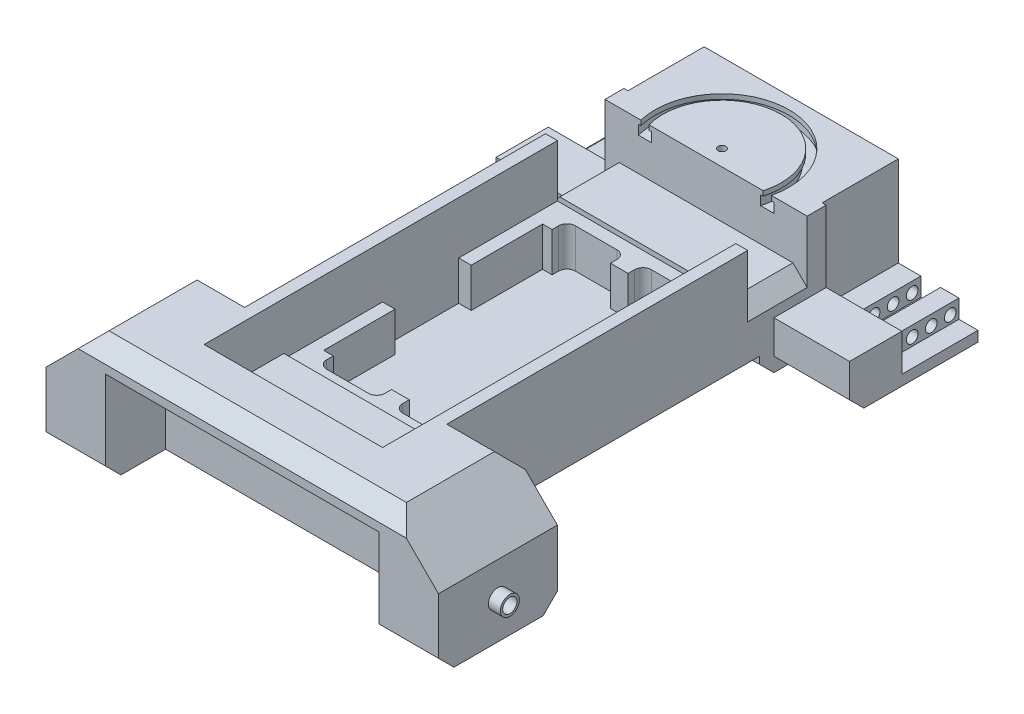
SolidWorks part; units mm, degrees
ref_plane "Front Plane" through (0, 0, 0) normal (0, 0, 1) x (1, 0, 0)
ref_plane "Top Plane" through (0, 0, 0) normal (0, 1, 0) x (1, 0, 0)
ref_plane "Right Plane" through (0, 0, 0) normal (1, 0, 0) x (0, 0, -1)
sketch "Sketch1" plane through (0, 0, 0) normal (0, 1, 0) x (1, 0, 0)
  line L1 (0, 0) -> (75, 0)
  line L2 (0, 0) -> (0, 115)
  line L3 (0, 115) -> (75, 115)
  line L4 (75, 0) -> (75, 115)
  line L5 (-5, -5) -> (80, -5)
  line L6 (-5, -5) -> (-5, 120)
  line L7 (-5, 120) -> (80, 120)
  line L8 (80, -5) -> (80, 120)
  line L9 (-5, 120) -> (80, 120)
  line L10 (-5, 120) -> (-5, 180)
  line L11 (-5, 180) -> (80, 180)
  line L12 (80, 120) -> (80, 180)
  line L13 (-5, -5) -> (80, -5)
  line L14 (-5, -5) -> (-5, -30)
  line L15 (-5, -30) -> (80, -30)
  line L16 (80, -5) -> (80, -30)
  line L17 (-5, 180) -> (-45, 180)
  line L18 (-5, 180) -> (-5, 120)
  line L19 (-5, 120) -> (-45, 120)
  line L20 (-45, 180) -> (-45, 120)
  line L21 (80, 180) -> (120, 180)
  line L22 (80, 180) -> (80, 120)
  line L23 (80, 120) -> (120, 120)
  line L24 (120, 180) -> (120, 120)
  line L25 (-5, -30) -> (-45, -30)
  line L26 (-5, -30) -> (-5, -5)
  line L27 (-5, -5) -> (-45, -5)
  line L28 (-45, -30) -> (-45, -5)
  line L29 (80, -30) -> (120, -30)
  line L30 (80, -30) -> (80, -5)
  line L31 (80, -5) -> (120, -5)
  line L32 (120, -30) -> (120, -5)
  dimension "D1" = 115
  dimension "D2" = 75
  dimension "D3" = 125
  dimension "D4" = 85
  dimension "D5" = 5
  dimension "D6" = 5
  dimension "D7" = 60
  dimension "D8" = 25
  dimension "D9" = 85
  dimension "D10" = 40
  dimension "D11" = 40
  dimension "D12" = 40
extrude "Boss-Extrude1" add sketch "Sketch1" against normal blind 22 contours L17 L20 L19 L10 | L7 L12 L11 L10 | L24 L21 L12 L23 | L5 L8 L7 L6 L4 L1 L2 L3 | L28 L25 L14 L27 | L16 L5 L14 L15 | L29 L32 L31 L16 region at (-3.4884, 0, -57.5) region at (37.5, 0, 17.5) region at (-25, 0, 17.5) region at (100, 0, 17.5) region at (37.5, 0, -150) region at (-25, 0, -150) region at (100, 0, -150)
sketch "Sketch2" plane through (0, -22, 0) normal (0, -1, 0) x (1, 0, 0)
  line L0 (5.25, -11.5) -> (69.75, -11.5)
  line L1 (0, -57.5) -> (75, -57.5)
  line L2 (0, -57.5) -> (0, -73.5)
  line L3 (0, -73.5) -> (75, -73.5)
  line L4 (75, -57.5) -> (75, -73.5)
  line L5 (0, -77.21) -> (5.25, -77.21)
  line L6 (0, 0) -> (0, -115) construction
  line L7 (75, 0) -> (75, -115) construction
  line L8 (0, -77.21) -> (0, -37.79)
  line L9 (0, -57.5) -> (75, -57.5)
  line L10 (0, -57.5) -> (0, -41.5)
  line L11 (0, -41.5) -> (75, -41.5)
  line L12 (75, -57.5) -> (75, -41.5)
  line L13 (37.5, -41.5) -> (5.25, -41.5)
  line L14 (37.5, -41.5) -> (37.5, -11.5)
  line L15 (37.5, -11.5) -> (5.25, -11.5)
  line L16 (5.25, -41.5) -> (5.25, -11.5)
  line L17 (37.5, -11.5) -> (69.75, -11.5)
  line L18 (37.5, -11.5) -> (37.5, -41.5)
  line L19 (37.5, -41.5) -> (69.75, -41.5)
  line L20 (69.75, -11.5) -> (69.75, -41.5)
  line L21 (5.25, -73.5) -> (69.75, -73.5)
  line L22 (5.25, -73.5) -> (5.25, -103.5)
  line L23 (5.25, -103.5) -> (69.75, -103.5)
  line L24 (69.75, -73.5) -> (69.75, -103.5)
  line L25 (9.275, -103.5) -> (33.775, -103.5)
  line L26 (9.275, -103.5) -> (9.275, -106.25)
  line L27 (12.775, -109.75) -> (30.275, -109.75)
  line L28 (33.775, -103.5) -> (33.775, -106.25)
  line L29 (41.223, -103.5) -> (65.723, -103.5)
  line L30 (41.223, -103.5) -> (41.223, -106.25)
  line L31 (44.723, -109.75) -> (62.223, -109.75)
  line L32 (65.723, -103.5) -> (65.723, -106.25)
  line L33 (0, -37.79) -> (5.25, -37.79)
  line L34 (5.25, -77.21) -> (5.25, -37.79)
  line L35 (69.75, -37.79) -> (75, -37.79)
  line L36 (69.75, -37.79) -> (69.75, -77.21)
  line L37 (69.75, -77.21) -> (75, -77.21)
  line L38 (75, -37.79) -> (75, -77.21)
  line L39 (65.723, -11.5) -> (65.723, -8.75)
  line L40 (44.723, -5.25) -> (62.223, -5.25)
  line L41 (41.223, -11.5) -> (41.223, -8.75)
  line L42 (33.775, -11.5) -> (33.775, -8.75)
  line L43 (12.775, -5.25) -> (30.275, -5.25)
  line L44 (9.275, -11.5) -> (9.275, -8.75)
  line L46 (0, 0) -> (75, 0)
  line L47 (0, 0) -> (0, -115)
  line L48 (0, -115) -> (75, -115)
  line L49 (75, 0) -> (75, -115)
  line L50 (-5, 5) -> (80, 5)
  line L51 (-5, 5) -> (-5, -120)
  line L52 (-5, -120) -> (80, -120)
  line L53 (80, 5) -> (80, -120)
  arc A0 (62.223, -109.75) -> (65.723, -106.25) centre (62.223, -106.25) ccw
  arc A1 (41.223, -106.25) -> (44.723, -109.75) centre (44.723, -106.25) ccw
  arc A2 (30.275, -109.75) -> (33.775, -106.25) centre (30.275, -106.25) ccw
  arc A3 (9.275, -106.25) -> (12.775, -109.75) centre (12.775, -106.25) ccw
  arc A4 (9.275, -8.75) -> (12.775, -5.25) centre (12.775, -8.75) cw
  arc A5 (30.275, -5.25) -> (33.775, -8.75) centre (30.275, -8.75) cw
  arc A6 (41.223, -8.75) -> (44.723, -5.25) centre (44.723, -8.75) cw
  arc A7 (62.223, -5.25) -> (65.723, -8.75) centre (62.223, -8.75) cw
  point P38 (9.275, -109.75)
  point P63 (9.275, -5.25)
  line M17 (80, -120) -> (80, 5)
  line M23 (-5, 5) -> (-5, -120)
  line M26 (75, 0) -> (75, -115)
  line M27 (75, -115) -> (0, -115)
  line M28 (0, -115) -> (0, 0)
  line M29 (0, 0) -> (75, 0)
  dimension "D14" = 3.5
  dimension "D1" = 16
  dimension "D2" = 75
  dimension "D3" = 16
  dimension "D6" = 32.25
  dimension "D7" = 30
  dimension "D8" = 6.25
  dimension "D9" = 24.5
  dimension "D10" = 4.025
  dimension "D11" = 24.5
  dimension "D12" = 64.5
  dimension "D13" = 4.027
  dimension "D15" = 39.42
  dimension "D16" = 3.71
  dimension "D17" = 3.71
extrude "Boss-Extrude2" add sketch "Sketch2" along normal blind 16.5 contours A3 L26 L23 L22 L5 L37 L24 L32 A0 L31 A1 L30 L28 A2 L27 M28 M27 M26 | L52 L50 L8 M23 M17 M29 M26 M27 M28 | L40 A7 L39 L17 L20 L35 L33 L16 L0 L44 A4 L43 A5 L42 L15 L41 A6 M26 M29 M28 | L24 L37 L3 M26 | L35 L20 L11 M26 | L33 L8 L11 L16 | L22 L3 L5 M28 region at (37.5004, -22, -10.9883) region at (2.625, -22, -39.645) region at (72.375, -22, -39.645) region at (2.625, -22, -75.355) region at (72.375, -22, -75.355) region at (37.5004, -22, -104.0117) region at (37.5, -22, 3.4884)
sketch "Sketch4" plane through (0, -38.5, 0) normal (0, -1, 0) x (1, 0, 0)
  line L1 (-5, 5) -> (80, 5)
  line L2 (-5, 5) -> (-5, -120)
  line L3 (-5, -120) -> (80, -120)
  line L4 (80, 5) -> (80, -120)
extrude "Boss-Extrude3" add sketch "Sketch4" along normal blind 2.5
sketch "Sketch5" plane through (0, 0, 0) normal (0, 1, 0) x (1, 0, 0)
  line L1 (-45, 180) -> (120, 180)
  line L2 (-45, 180) -> (-45, 120)
  line L3 (-45, 120) -> (120, 120)
  line L4 (120, 180) -> (120, 120)
  line L5 (-45, -5) -> (120, -5)
  line L6 (-45, -5) -> (-45, -30)
  line L7 (-45, -30) -> (120, -30)
  line L8 (120, -5) -> (120, -30)
  line M1 (120, 180) -> (-45, 180)
  line M2 (-45, 180) -> (-45, 120)
  line M3 (-45, 120) -> (-5, 120)
  line M5 (-5, -5) -> (-45, -5)
  line M6 (-45, -5) -> (-45, -30)
  line M7 (-45, -30) -> (120, -30)
  line M8 (120, -30) -> (120, -5)
  line M9 (120, -5) -> (80, -5)
  line M11 (80, 120) -> (120, 120)
  line M12 (120, 120) -> (120, 180)
extrude "Boss-Extrude4" add sketch "Sketch5" against normal blind 50 contours L3 M3 M11 M12 M1 M2 | L5 M5 M6 M7 M8 M9 region at (37.5, 0, -150) region at (37.5, 0, 17.5)
sketch "Sketch9" plane through (0, 0, 0) normal (0, 1, 0) x (1, 0, 0)
  line L0 (120, 180) -> (120, 120) construction
  line L1 (-45, 120) -> (120, 120)
  line L2 (-45, 120) -> (-45, 126)
  line L3 (-45, 126) -> (120, 126)
  line L4 (120, 120) -> (120, 126)
  line L6 (-5, 120) -> (80, 120)
  line L7 (-5, 120) -> (-5, 126)
  line L8 (-5, 126) -> (80, 126)
  line L9 (80, 120) -> (80, 126)
  line M3 (-45, 180) -> (-45, 120)
  line M4 (-45, 120) -> (-5, 120)
  line M12 (80, 120) -> (120, 120)
  line M13 (120, 120) -> (120, 180)
  dimension "D1" = 6
extrude "Cut-Extrude2" cut sketch "Sketch9" against normal blind 50 contours L7 L3 M4 M3 | L9 L3 M12 M13 region at (-25, 0, -123) region at (100, 0, -123)
sketch "Sketch8" plane through (0, 0, -180) normal (0, 0, -1) x (-1, 0, 0)
  line L0 (-120, -50) -> (45, -50) construction
  line L1 (-120, 0) -> (-87.815, 0)
  line L2 (-120, 0) -> (-120, -45.675)
  line L3 (-120, -45.675) -> (-87.815, -45.675)
  line L4 (-87.815, 0) -> (-87.815, -45.675)
  line L6 (-120, -45.675) -> (-111.815, -45.675)
  line L7 (-120, -45.675) -> (-120, -50)
  line L8 (-120, -50) -> (-111.815, -50)
  line L9 (-111.815, -45.675) -> (-111.815, -50)
  line L10 (-103.815, -45.675) -> (-96.065, -45.675)
  line L11 (-103.815, -45.675) -> (-103.815, -37.925)
  line L12 (-103.815, -37.925) -> (-96.065, -37.925)
  line L13 (-96.065, -45.675) -> (-96.065, -37.925)
  line L14 (-87.815, -45.675) -> (-78.315, -45.675)
  line L15 (-87.815, -45.675) -> (-87.815, -37.925)
  line L16 (-87.815, -37.925) -> (-78.315, -37.925)
  line L17 (-78.315, -45.675) -> (-78.315, -37.925)
  line L18 (-78.315, -45.675) -> (-87.815, -45.675)
  line L19 (-78.315, -45.675) -> (-78.315, 0)
  line L20 (-78.315, 0) -> (-87.815, 0)
  line L21 (-87.815, -45.675) -> (-87.815, 0)
  line M4 (45, 0) -> (-120, 0)
  line M5 (-120, 0) -> (-120, -50)
  line M6 (-120, -50) -> (45, -50)
  dimension "D1" = 32.185
  dimension "D2" = 4.325
  dimension "D3" = 8.185
  dimension "D4" = 7.75
  dimension "D5" = 16.185
  dimension "D6" = 9.5
extrude "Cut-Extrude1" cut sketch "Sketch8" against normal blind 32 contours L13 L3 L4 L11 L12 M4 M5 | L9 L3 M5 M6 | L16 L19 L4 M4 region at (104.0765, -22.0297, -180) region at (83.065, -18.9625, -180) region at (115.9075, -47.8375, -180)
sketch "Sketch10" plane through (0, 0, 0) normal (0, 1, 0) x (1, 0, 0)
  line L1 (120, 148) -> (80, 148)
  line L2 (120, 148) -> (120, 126)
  line L3 (120, 126) -> (80, 126)
  line L4 (80, 148) -> (80, 126)
extrude "Cut-Extrude3" cut sketch "Sketch10" against normal blind 30
sketch "Sketch11" plane through (120, 0, 0) normal (1, 0, 0) x (0, 0, -1)
  line L5 (126, -30) -> (148, -30)
  line L6 (126, -30) -> (126, -50)
  line L7 (126, -50) -> (148, -50)
  line L8 (148, -30) -> (148, -50)
extrude "Cut-Extrude4" cut sketch "Sketch11" against normal up to surface (8.185 mm away) up to face at (111.815, -47.8375, -164)
sketch "Sketch12" plane through (0, 0, 0) normal (0, 1, 0) x (1, 0, 0)
  line L0 (80, -5) -> (80, 148) construction
  line L1 (0, 115) -> (75, 115)
  line L2 (0, 115) -> (0, 140)
  line L3 (0, 140) -> (75, 140)
  line L4 (75, 115) -> (75, 140)
  line L5 (75, 140) -> (80, 140)
  line L6 (75, 140) -> (75, 115)
  line L7 (75, 115) -> (80, 115)
  line L8 (80, 140) -> (80, 115)
  line M1 (80, -5) -> (80, 148)
  line M2 (80, 148) -> (78.315, 148)
  line M16 (0, 115) -> (75, 115)
  dimension "D1" = 75
  dimension "D2" = 25
extrude "Cut-Extrude5" cut sketch "Sketch12" against normal blind 20 contours L4 L3 L2 M16 | L4 L7 L5 M1 M2 region at (37.5, 0, -127.5) region at (77.5, 0, -127.5)
ref_plane "Plane1" through (37.5, 0, 0) normal (-1, 0, 0) x (0, 0, 1)
mirror "Mirror4" about plane through (37.5, 0, 0) normal (-1, 0, 0) of "Cut-Extrude1", "Cut-Extrude3", "Cut-Extrude4", "Cut-Extrude5"
chamfer "Chamfer1" distance 6 angle 45 2 edges at (80, -20, -127.5) (-5, -20, -127.5)
chamfer "Chamfer2" distance 6 angle 45 4 edges at (95.9075, -50, -126) (-20.9075, -50, -126) (37.5, -50, 5) (37.5, -50, -120)
sketch "Sketch14" plane through (0, 0, 0) normal (0, 1, 0) x (1, 0, 0)
  line L1 (0, 0) -> (75, 0)
  line L2 (0, 0) -> (0, -17.5)
  line L3 (0, -17.5) -> (75, -17.5)
  line L4 (75, 0) -> (75, -17.5)
  dimension "D1" = 17.5
  dimension "D2" = 75
extrude "Cut-Extrude6" cut sketch "Sketch14" against normal blind 20
sketch "Sketch18" plane through (-45, 0, 0) normal (-1, 0, 0) x (0, 0, 1)
  line L1 (30, 0) -> (55, 0)
  line L2 (30, 0) -> (30, -50)
  line L3 (30, -50) -> (55, -50)
  line L4 (55, 0) -> (55, -50)
  dimension "D1" = 25
extrude "Boss-Extrude5" add sketch "Sketch18" against normal up to surface (165 mm away) up to face at (120, -28.8, 16.2)
chamfer "Chamfer3" distance 16 angle 45 1 edges at (37.5, 0, 17.5)
sketch "Sketch19" plane through (-45, 0, 0) normal (-1, 0, 0) x (0, 0, 1)
  line L0 (-232.325, -34.24) -> (88.5931, -34.24) construction
  circle A0 centre (30, -34.24) radius 3
  dimension "D1" = 6
extrude "Cut-Extrude7" cut sketch "Sketch19" against normal blind 20
chamfer "Chamfer4" distance 6.5 angle 45 1 edges at (37.5, -50, 55)
chamfer "Chamfer5" distance 6.5 angle 45 2 edges at (100, 0, 5) (-25, 0, 5)
sketch "Sketch20" plane through (0, -50, 0) normal (0, -1, 0) x (1, 0, 0)
  line L0 (-45, 29.75) -> (-20, 29.75)
  line L1 (-45, 11) -> (-45, 48.5) construction
  line L2 (120, 29.75) -> (95, 29.75)
  line L3 (120, 48.5) -> (120, 11) construction
  line L4 (95, 29.75) -> (-20, 29.75)
  line L5 (-45, 55) -> (120, 55) construction
  line L6 (-20, 29.75) -> (95, 29.75)
  line L7 (-20, 29.75) -> (-20, 55)
  line L8 (-20, 55) -> (95, 55)
  line L9 (95, 29.75) -> (95, 55)
  line M2 (120, 48.5) -> (-45, 48.5)
  dimension "D1" = 25
  dimension "D2" = 25
extrude "Cut-Extrude8" cut sketch "Sketch20" against normal blind 20 contours L4 L9 L7 M2 | L9 L8 L7 M2 region at (37.5, -50, 39.125) region at (37.5, -50, 51.75)
mirror "Mirror5" about plane through (37.5, 0, 0) normal (-1, 0, 0) of "Cut-Extrude7"
chamfer "Chamfer6" distance 6.5 angle 45 1 edges at (37.5, 0, 55)
chamfer "Chamfer8" distance 20 angle 45 1 edges at (37.5, -30, 55)
chamfer "Chamfer9" distance 20 angle 45 2 edges at (-45, 0, 30) (120, 0, 30)
sketch "Sketch21" plane through (-36.815, 0, 0) normal (-1, 0, 0) x (0, 0, 1)
  circle A0 centre (-176.325, -42.24) radius 2.45
  circle A1 centre (-168.325, -42.24) radius 2.45
  circle A2 centre (-160.325, -42.24) radius 2.45
extrude "Cut-Extrude9" cut sketch "Sketch21" against normal blind 30
mirror "Mirror6" about plane through (37.5, 0, 0) normal (-1, 0, 0) of "Cut-Extrude9"
sketch "Sketch22" plane through (-45, 0, 0) normal (-1, 0, 0) x (0, 0, 1)
  circle A4 centre (30, -34.24) radius 3
  circle A5 centre (30, -34.24) radius 4
  dimension "D1" = 8
extrude "Boss-Extrude6" add sketch "Sketch22" along normal blind 5
mirror "Mirror7" about plane through (37.5, 0, 0) normal (-1, 0, 0) of "Boss-Extrude6"
sketch "Sketch23" plane through (0, 0, 0) normal (0, 1, 0) x (1, 0, 0)
  circle A0 centre (37.5, 173.2662) radius 2.7
  circle A2 centre (37.5, 146.7069) radius 1.65
  circle A3 centre (37.5, 146.7069) radius 29.2593
  circle A4 centre (37.5, 146.7069) radius 23.8593
  line M2 (-5, 140) -> (80, 140)
  dimension "D1" = 5.4
  dimension "D2" = 3.3
extrude "Cut-Extrude10" cut sketch "Sketch23" against normal blind 6 contours A4 A3 A0 M2 | A4 A0 A3 M2 | A0 | A2 region at (37.5, 0, -173.2662) region at (39.737, 0, -175.5033) region at (34.3364, 0, -173.2662) region at (37.5, 0, -146.7069)
sketch "Sketch24" plane through (0, 0, 0) normal (0, 1, 0) x (1, 0, 0)
  line L0 (37.5, 175.9662) -> (37.5, 170.5662)
  line L1 (-5, 140) -> (80, 140)
  arc A0 (65.9802, 140) -> (9.0198, 140) centre (37.5, 146.7069) ccw construction
  arc A1 (60.3972, 140) -> (14.6028, 140) centre (37.5, 146.7069) ccw construction
  circle A2 centre (37.5, 173.2662) radius 1.65
  circle A3 centre (37.5, 146.7069) radius 24.9093
  circle A4 centre (37.5, 146.7069) radius 28.2093
  circle A5 centre (37.5, 146.7069) radius 30.9904
  circle A6 centre (37.5, 146.7069) radius 1.6586
  arc M1 (9.0198, 140) -> (65.9802, 140) centre (37.5, 146.7069) cw
  line M2 (65.9802, 140) -> (80, 140)
  dimension "D1" = 3.3
  dimension "D2" = 26.5593
extrude "Boss-Extrude7" add sketch "Sketch24" against normal blind 2 contours A4 L1 L0 M1 | A5 L1 M2 M1 | A4 L0 L1 M1 | L1 A3 region at (60.075, 0, -164.5832) region at (37.0364, 0, -175.4412) region at (13.9928, 0, -165.3213) region at (37.5, 0, -153.8084)
